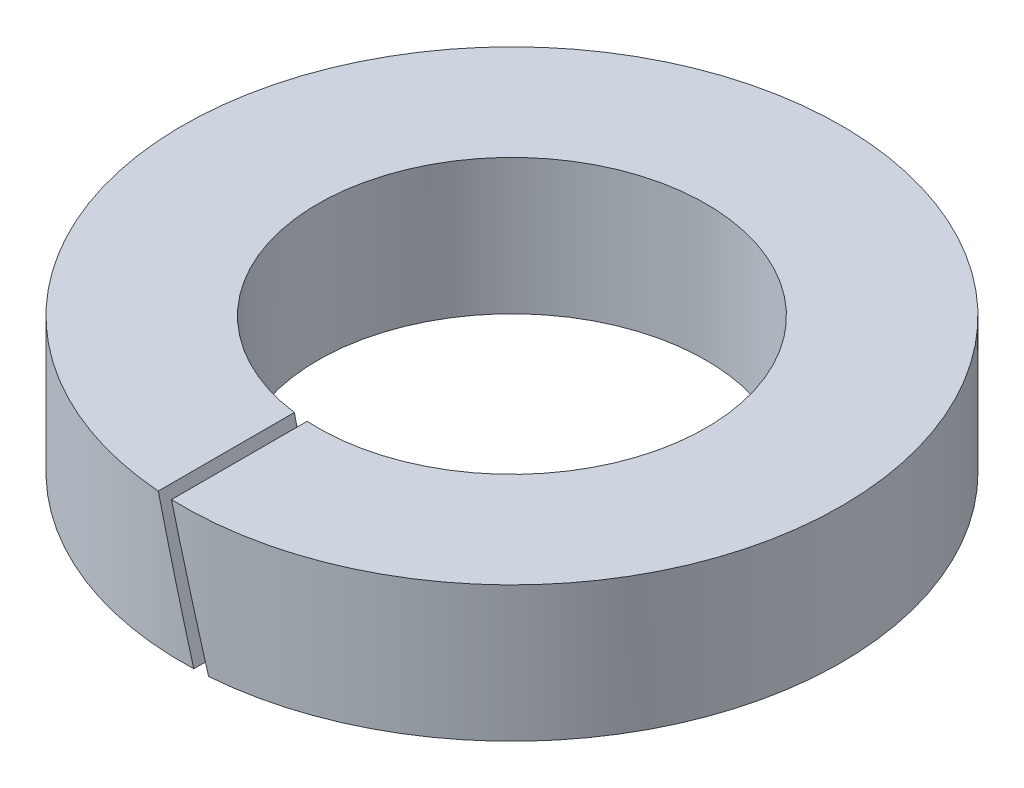
SolidWorks part; units mm, degrees
revolve "Base" add sketch "Esquisse1" angle 360 about L0
sketch "Esquisse1" plane through (0, 0, 0) normal (0, 0, 1) x (1, 0, 0)
  line L0 (0, 0.5) -> (0, -0.5) construction
  line L1 (2.15, 0) -> (-2.15, 0) construction
  line L2 (2.15, 0) -> (3.65, 0)
  line L3 (2.15, 0) -> (2.15, 1.5)
  line L4 (2.15, 1.5) -> (3.65, 1.5)
  line L5 (3.65, 0) -> (3.65, 1.5)
  line L6 (3.65, 0) -> (-3.65, 0) construction
  dimension "Rpas" = 2.15
  dimension "Rext" = 3.65
  dimension "Epaisseur" = 1.5
  dimension "Diamètre de passage" = 4.3
  dimension "Diamètre extérieur" = 7.3
ref_plane "Plan1" through (0, 0, 0) normal (0, 0, 1) x (1, 0, 0)
ref_plane "Plan2" through (0, 0, 0) normal (0, 1, 0) x (1, 0, 0)
ref_plane "Plan3" through (0, 0, 0) normal (1, 0, 0) x (0, 0, -1)
ref_axis "Axe" through (0, 13.2259, 0) along (0, -1, 0)
ref_plane "Plan Fente" through (0, 0, 3.65) normal (0, 0, 1) x (1, 0, 0)
sketch "Esquisse2" plane through (0, 0, 3.65) normal (0, 0, 1) x (1, 0, 0)
  line L0 (0, 0.75) -> (0.4019, -0.75)
  line L1 (0, 0) -> (0, 1.5) construction
  line L2 (3.65, 1.5) -> (-3.65, 1.5) construction
  line L3 (0, 0.75) -> (-0.4019, 2.25)
  dimension "D1" = 15
extrude "Fente" cut sketch "Esquisse2" against normal up to next thin thin type mid plane wall 0.15
equation "\"Rext@Esquisse1\" = \"Diamètre extérieur@Esquisse1\"/2"
equation "\"Rpas@Esquisse1\" = \"Diamètre de passage@Esquisse1\"/2"
equation "\"ep@Esquisse2\" = \"Epaisseur@Esquisse1\""
equation "\"Pp@Plan Fente\" = \"Rext@Esquisse1\""
equation "\"Lf@Fente\" = \"ep@Esquisse2\"/10"
